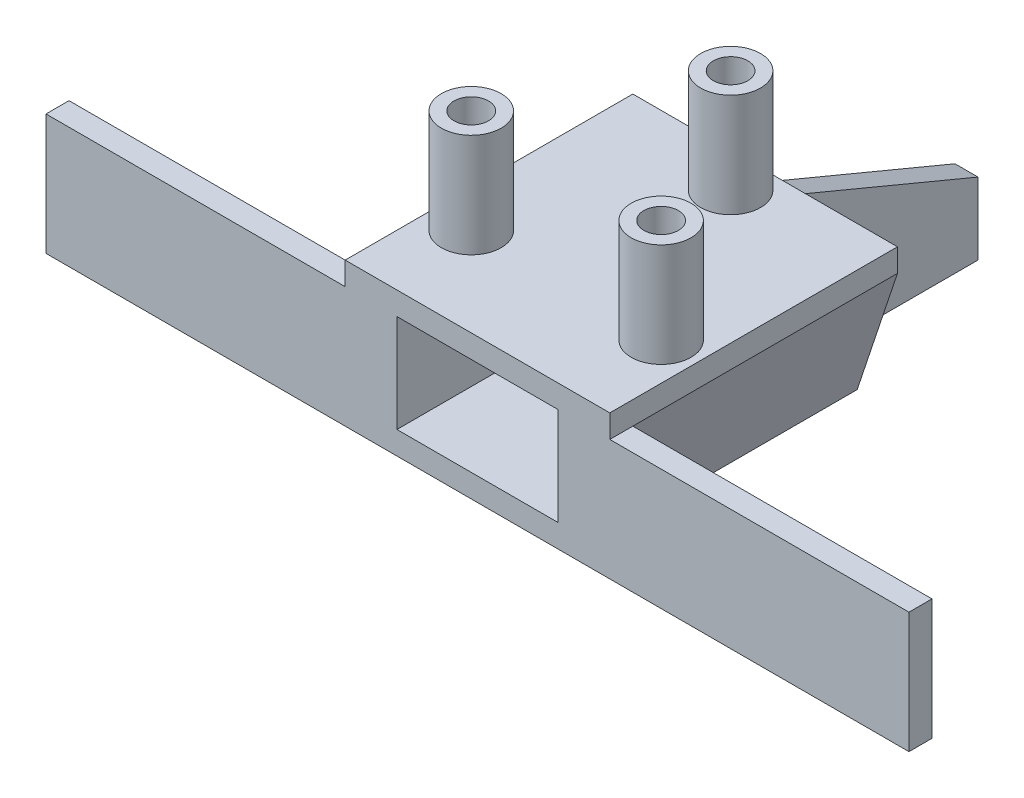
SolidWorks part; units mm, degrees
ref_plane "Front Plane" through (0, 0, 0) normal (0, 0, 1) x (1, 0, 0)
ref_plane "Top Plane" through (0, 0, 0) normal (0, 1, 0) x (1, 0, 0)
ref_plane "Right Plane" through (0, 0, 0) normal (1, 0, 0) x (0, 0, -1)
sketch "Sketch1" plane through (0, 0, 0) normal (0, 1, 0) x (1, 0, 0)
  line L0 (0, 0) -> (-8.25, -14.2894) construction
  line L1 (-8.25, -14.2894) -> (8.25, -14.2894) construction
  line L2 (8.25, -14.2894) -> (0, 0) construction
  circle A0 centre (-8.25, -14.2894) radius 2.6
  circle A1 centre (0, 0) radius 2.6
  circle A2 centre (8.25, -14.2894) radius 2.6
  circle A3 centre (0, 0) radius 1.5
  circle A4 centre (-8.25, -14.2894) radius 1.5
  circle A5 centre (8.25, -14.2894) radius 1.5
  dimension "D1" = 5.2
  dimension "D3" = 3
  dimension "D2" = 16.5
extrude "Boss-Extrude1" add sketch "Sketch1" along normal blind 9
sketch "Sketch2" plane through (0, 0, 0) normal (0, 1, 0) x (1, 0, 0)
  line L0 (0, 0) -> (0, 3) construction
  line L1 (-11.5, 3) -> (11.5, 3)
  line L2 (-11.5, 3) -> (-11.5, -22)
  line L3 (-11.5, -22) -> (11.5, -22)
  line L4 (11.5, 3) -> (11.5, -22)
  dimension "D1" = 23
  dimension "D2" = 25
  dimension "D3" = 3
extrude "Boss-Extrude2" add sketch "Sketch2" against normal blind 12.5
sketch "Sketch3" plane through (0, 0, -3) normal (0, 0, -1) x (-1, 0, 0)
  line L0 (-11.5, -12.5) -> (11.5, -12.5) construction
  line L1 (7, -10.5) -> (-7, -10.5)
  line L2 (7, -10.5) -> (7, -2)
  line L3 (7, -2) -> (-7, -2)
  line L4 (-7, -10.5) -> (-7, -2)
  line L5 (0, -10.5) -> (0, -12.5) construction
  dimension "D1" = 8.5
  dimension "D2" = 2
  dimension "D3" = 14
extrude "Cut-Extrude1" cut sketch "Sketch3" against normal through all from offset 2 offset against normal yes
ref_plane "Plane1" through (0, 0, 0) normal (-1, 0, 0) x (0, 0, 1)
sketch "Sketch4" plane through (0, 0, 0) normal (-1, 0, 0) x (0, 0, 1)
  line L0 (-3, -12.5) -> (22, -12.5) construction
  line L1 (22, -2) -> (20, -2)
  line L2 (22, -2) -> (22, -12.5)
  line L3 (22, -12.5) -> (20, -12.5)
  line L4 (20, -2) -> (20, -12.5)
  dimension "D1" = 2
  dimension "D2" = 10.5
extrude "Boss-Extrude3" add sketch "Sketch4" along normal blind 26 from surface starting at face at (-11.5, -6.25, 9.5)
extrude "Boss-Extrude4" add sketch "Sketch4<2>" against normal blind 26 from surface starting at face at (11.5, -6.25, 9.5)
sketch "Sketch4<2>" plane through (0, 0, 0) normal (-1, 0, 0) x (0, 0, 1) same geometry as "Sketch4"
sketch "Sketch5" plane through (0, 0, -3) normal (0, 0, -1) x (-1, 0, 0)
  line L0 (-11.5, 0) -> (11.5, 0) construction
  line L1 (-1.5, -12.5) -> (-3.5, -12.5)
  line L2 (-1.5, -12.5) -> (-1.5, 0)
  line L3 (-1.5, 0) -> (-3.5, 0)
  line L4 (-3.5, -12.5) -> (-3.5, 0)
  line L5 (-11.5, -12.5) -> (11.5, -12.5) construction
  dimension "D1" = 2
  dimension "D2" = 1.5
extrude "Boss-Extrude5" add sketch "Sketch5" along normal blind 15
sketch "Sketch6" plane through (0, 0, -3) normal (0, 0, 1) x (1, 0, 0)
  line L0 (-11.5, -2) -> (-8, -12.5)
  line L1 (-37.5, -12.5) -> (37.5, -12.5) construction
  line L2 (-8, -12.5) -> (-11.5, -12.5)
  line L3 (-11.5, -12.5) -> (-11.5, -2)
  line L4 (11.5, -2) -> (11.5, -12.5)
  line L5 (11.5, -12.5) -> (8, -12.5)
  line L6 (8, -12.5) -> (11.5, -2)
  dimension "D1" = 1
  dimension "D2" = 1
  dimension "D3" = 2
  dimension "D4" = 2
extrude "Cut-Extrude2" cut sketch "Sketch6" along normal up to surface (23 mm away) up to face at (-27.75, -8.5625, 20)
sketch "Sketch7" plane through (1.5, 0, 0) normal (-1, 0, 0) x (0, 0, 1)
  line L0 (-18, 0) -> (-18, -6.25)
  line L2 (-18, -12.5) -> (-18, 0) construction
  line L3 (-18, -6.25) -> (-3, 0)
  line L4 (-3, 0) -> (-18, 0)
extrude "Cut-Extrude3" cut sketch "Sketch7" against normal up to surface (2 mm away) up to face at (3.5, -4.6875, -14.25)
